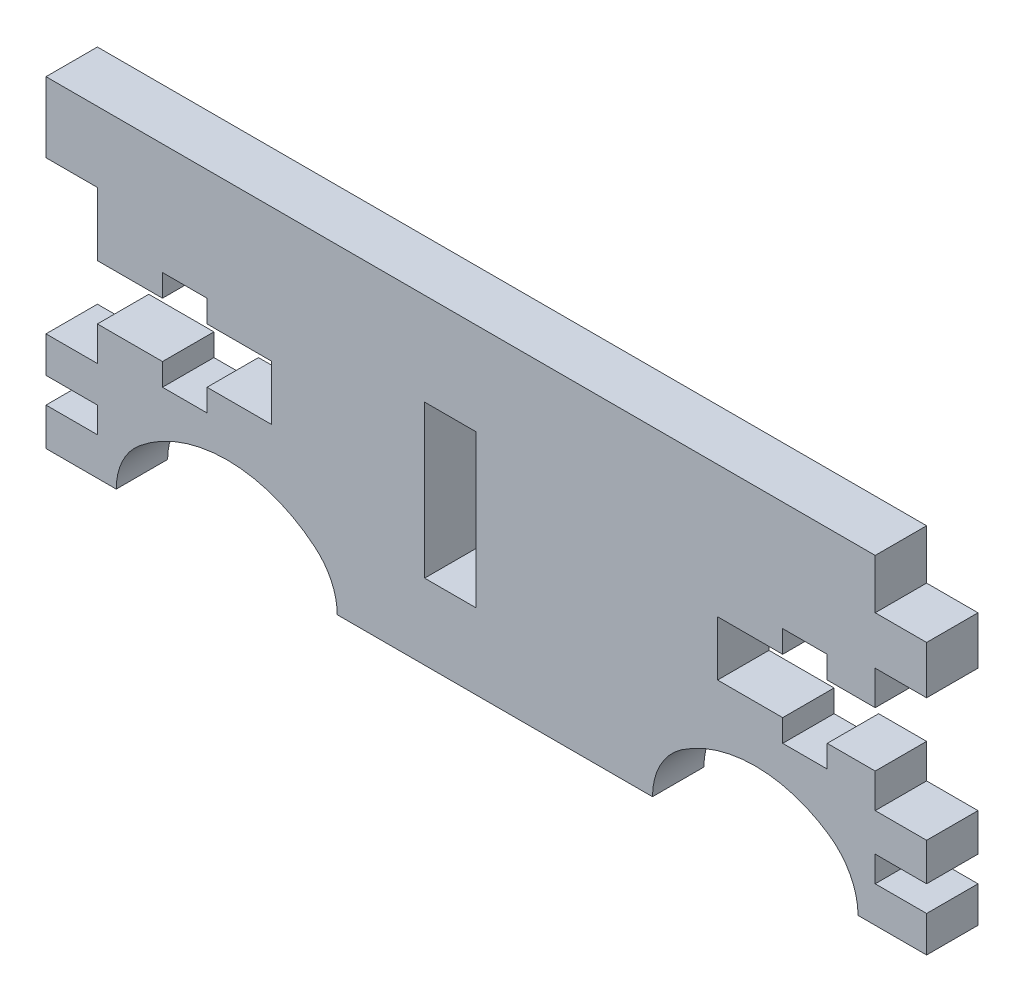
SolidWorks part; units mm, degrees
ref_plane "Plan de face" through (0, 0, 0) normal (0, 0, 1) x (1, 0, 0)
ref_plane "Plan de dessus" through (0, 0, 0) normal (0, 1, 0) x (1, 0, 0)
ref_plane "Plan de droite" through (0, 0, 0) normal (1, 0, 0) x (0, 0, -1)
sketch "Esquisse1" plane through (0, 0, 0) normal (0, 0, 1) x (1, 0, 0)
  line L0 (143.0303, 1474.6909) -> (194.4303, 1474.6909) construction
  line L1 (40.7233, 1326.2087) -> (92.1233, 1326.2087) construction
  line L2 (40.7065, 1340.1344) -> (89.1065, 1340.1344)
  line L3 (89.1065, 1340.1344) -> (89.1065, 1337.2344)
  line L4 (89.1065, 1337.2344) -> (92.1065, 1337.2344)
  line L5 (92.1065, 1337.2344) -> (92.1065, 1334.4344)
  line L6 (92.1065, 1334.4344) -> (89.1065, 1334.4344)
  line L7 (89.1065, 1334.4344) -> (89.1065, 1332.4343)
  line L8 (89.1065, 1332.4343) -> (86.3065, 1332.4343)
  line L9 (86.3065, 1332.4343) -> (86.3065, 1333.7343)
  line L10 (86.3065, 1333.7343) -> (83.7065, 1333.7343)
  line L11 (83.7065, 1333.7343) -> (83.7065, 1332.4343)
  line L12 (83.7065, 1332.4343) -> (79.9065, 1332.4343)
  line L13 (79.9065, 1332.4343) -> (79.9065, 1329.2343)
  line L14 (79.9065, 1329.2343) -> (83.7065, 1329.2343)
  line L15 (83.7065, 1329.2343) -> (83.7065, 1327.9343)
  line L16 (83.7065, 1327.9343) -> (86.3065, 1327.9343)
  line L17 (86.3065, 1327.9343) -> (86.3065, 1329.2343)
  line L18 (86.3065, 1329.2343) -> (89.1065, 1329.2343)
  line L19 (89.1065, 1329.2343) -> (89.1065, 1327.2343)
  line L20 (89.1065, 1327.2343) -> (92.1065, 1327.2343)
  line L21 (92.1065, 1327.2343) -> (92.1065, 1325.0343)
  line L22 (92.1065, 1325.0343) -> (89.1065, 1325.0343)
  line L23 (89.1065, 1325.0343) -> (89.1065, 1323.5343)
  line L24 (89.1065, 1323.5343) -> (92.1065, 1323.5343)
  line L25 (92.1065, 1323.5343) -> (92.1065, 1321.4343)
  line L26 (92.1065, 1321.4343) -> (88.1046, 1321.4343)
  line L27 (76.1065, 1321.4344) -> (57.7065, 1321.4344)
  line L28 (44.8065, 1321.3344) -> (40.7065, 1321.3344)
  line L29 (40.7065, 1321.3344) -> (40.7065, 1323.5344)
  line L30 (40.7065, 1323.5344) -> (43.7065, 1323.5344)
  line L31 (43.7065, 1323.5344) -> (43.7065, 1325.0344)
  line L32 (43.7065, 1325.0344) -> (40.7065, 1325.0344)
  line L33 (40.7065, 1325.0344) -> (40.7065, 1327.1344)
  line L34 (40.7065, 1327.1344) -> (43.7065, 1327.1344)
  line L35 (43.7065, 1327.1344) -> (43.7065, 1329.1344)
  line L36 (43.7065, 1329.1344) -> (47.5065, 1329.1344)
  line L37 (47.5065, 1329.1344) -> (47.5065, 1327.8344)
  line L38 (47.5065, 1327.8344) -> (50.1065, 1327.8344)
  line L39 (50.1065, 1327.8344) -> (50.1065, 1329.1344)
  line L40 (50.1065, 1329.1344) -> (53.8565, 1329.1344)
  line L41 (53.8565, 1329.1344) -> (53.8565, 1332.3344)
  line L42 (53.8565, 1332.3344) -> (50.1065, 1332.3344)
  line L43 (50.1065, 1332.3344) -> (50.1065, 1333.6344)
  line L44 (50.1065, 1333.6344) -> (47.5065, 1333.6344)
  line L45 (47.5065, 1333.6344) -> (47.5065, 1332.3344)
  line L46 (47.5065, 1332.3344) -> (43.7065, 1332.3344)
  line L47 (43.7065, 1332.3344) -> (43.7065, 1336.0344)
  line L48 (43.7065, 1336.0344) -> (40.7065, 1336.0344)
  line L49 (40.7065, 1336.0344) -> (40.7065, 1340.1344)
  line L50 (44.8065, 1321.3344) -> (44.8065, 1324.9882) construction
  line L51 (62.8065, 1334.7344) -> (65.8065, 1334.7344)
  line L52 (62.8065, 1334.7344) -> (62.8065, 1325.8344)
  line L53 (62.8065, 1325.8344) -> (65.8065, 1325.8344)
  line L54 (65.8065, 1334.7344) -> (65.8065, 1325.8344)
  line L55 (57.7065, 1321.4344) -> (57.7065, 1325.2008) construction
  line L56 (66.9065, 1321.4344) -> (66.9065, 1323.5343) construction
  line L57 (76.1065, 1321.4344) -> (76.1065, 1326.8143) construction
  line L58 (88.1046, 1321.4343) -> (88.1046, 1326.2982) construction
  arc A0 (44.8065, 1321.3344) -> (46.1495, 1324.1955) centre (48.5256, 1321.3344) cw
  arc A1 (46.1495, 1324.1955) -> (56.4104, 1324.1955) centre (51.2799, 1318.0179) cw
  arc A2 (56.4104, 1324.1955) -> (57.7065, 1321.4344) centre (54.1173, 1321.4344) cw
  arc A6 (76.1065, 1321.4344) -> (77.8096, 1324.6619) centre (80.0163, 1321.4344) cw
  arc A7 (77.8096, 1324.6619) -> (86.4014, 1324.6619) centre (82.1055, 1318.3789) cw
  arc A8 (86.4014, 1324.6619) -> (88.1046, 1321.4343) centre (84.1946, 1321.4343) cw
  dimension "D6" = 2.9
  dimension "D47" = 16
  dimension "D48" = 3
  dimension "D1" = 51.4
  dimension "D2" = 51.4
  dimension "D3" = 48.4
  dimension "D4" = 1340.1344
  dimension "D5" = 40.7065
  dimension "D7" = 3
  dimension "D8" = 2.8
  dimension "D9" = 3
  dimension "D10" = 2.0001
  dimension "D11" = 2.8
  dimension "D12" = 2.6
  dimension "D13" = 1.3
  dimension "D14" = 3.8
  dimension "D15" = 3.8
  dimension "D16" = 3.2
  dimension "D17" = 3.2
  dimension "D18" = 7.7001
  dimension "D19" = 7.7001
  dimension "D20" = 1.3
  dimension "D21" = 2
  dimension "D22" = 3
  dimension "D23" = 3
  dimension "D24" = 2.2
  dimension "D25" = 1.5
  dimension "D26" = 2.1
  dimension "D27" = 4.0019
  dimension "D28" = 4.1
  dimension "D29" = 3
  dimension "D30" = 7.8
  dimension "D31" = 3.8
  dimension "D32" = 6.5
  dimension "D33" = 1.3
  dimension "D34" = 1.3
  dimension "D35" = 3.2
  dimension "D36" = 2.6
  dimension "D37" = 10.15
  dimension "D38" = 1.3
  dimension "D39" = 2.6
  dimension "D40" = 13
  dimension "D41" = 2.1
  dimension "D42" = 1.5
  dimension "D43" = 2.2
  dimension "D44" = 4.1
  dimension "D45" = 18.4
  dimension "D46" = 18.7
  dimension "D49" = 8.9
  dimension "D50" = 5.4
  dimension "D51" = 26.3
base flange "Tôle de base pliée1" sketch "Esquisse1" thickness 3 reverse thickness direction no parameters "D1"=1.5
sketch "Lignes de pliage1" [suppressed] plane through (0, 0, 0) normal (0, 1, 0) x (1, 0, 0)
sketch "Cube de visualisation1" [suppressed] plane through (0, 0, 0) normal (0, 1, 0) x (1, 0, 0)
sheet metal parameters "Tôlerie1" thickness 3 parameters "D1"=1.5
flat pattern "Etat déplié1" [suppressed]
sketch "Lignes de pliage2" plane through (0, 0, 0) normal (0, 1, 0) x (1, 0, 0)
sketch3d "Cube de visualisation2" [suppressed]
  line L0 (-43.4881, -0.0999, 0) -> (7.9119, -0.0999, 0) construction
  line L1 (-43.4881, 18.7001, 0) -> (7.9119, 18.7001, 0) construction
  line L2 (-43.4881, -0.0999, 0) -> (-43.4881, 18.7001, 0) construction
  line L3 (7.9119, -0.0999, 0) -> (7.9119, 18.7001, 0) construction
